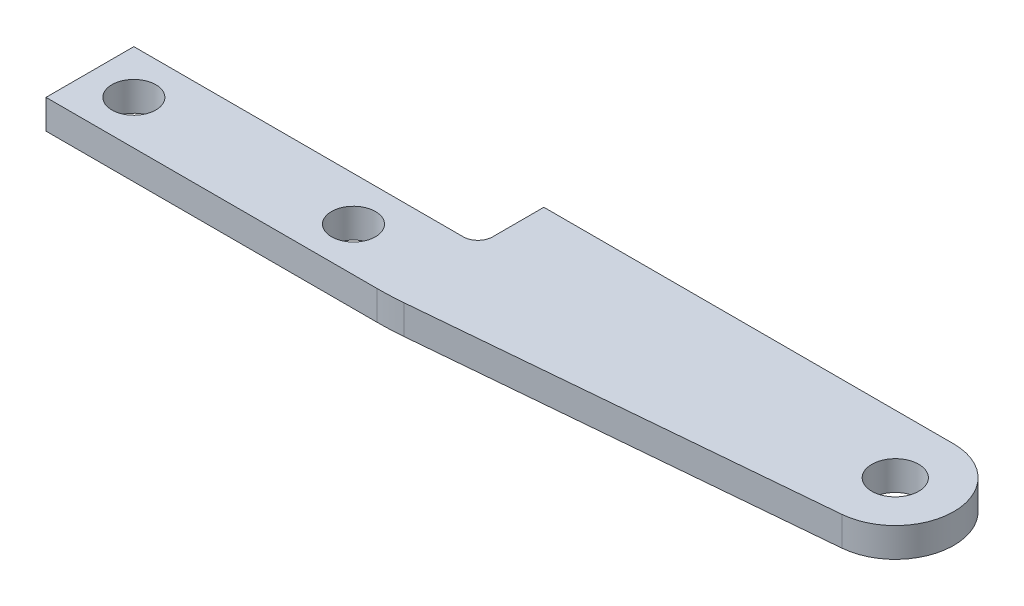
SolidWorks part; units mm, degrees
material "Thornel Mat VMA"
ref_plane "前视基准面" through (0, 0, 0) normal (0, 0, 1) x (1, 0, 0)
ref_plane "上视基准面" through (0, 0, 0) normal (0, 1, 0) x (1, 0, 0)
ref_plane "右视基准面" through (0, 0, 0) normal (1, 0, 0) x (0, 0, -1)
sketch "草图2" plane through (0, 0, 0) normal (0, 1, 0) x (1, 0, 0)
  line L7 (20.5, 3) -> (-3, 3)
  line L8 (-3, 3) -> (-3, -3)
  line L9 (-3, -3) -> (20.5, -3)
  line L15 (48.5, 7.5) -> (20.5, 7.5)
  line L16 (20.5, 7.5) -> (20.5, 3)
  line L17 (15, 0) -> (0, 0) construction
  line L18 (48.8535, -0.4843) -> (20.5, -3)
  circle A3 centre (0, 0) radius 1.5
  circle A4 centre (15, 0) radius 1.5
  arc A17 (48.8535, -0.4843) -> (48.5, 7.5) centre (48.5, 3.5) ccw
  circle A18 centre (48.5, 3.5) radius 1.6
  dimension "D4" = 51.5
  dimension "D6" = 3
  dimension "D7" = 3
  dimension "D8" = 3
  dimension "D12" = 4.5
  dimension "D9" = 3.2
  dimension "D10" = 4
  dimension "D2" = 23.5
  dimension "D3" = 6
  dimension "D5" = 15
extrude "凸台-拉伸2" add sketch "草图2" along normal blind 2
fillet "圆角1" radius 1 1 edges at (20.5, 1, -3)
fillet "圆角2" radius 20 1 edges at (20.5, 1, 3)
